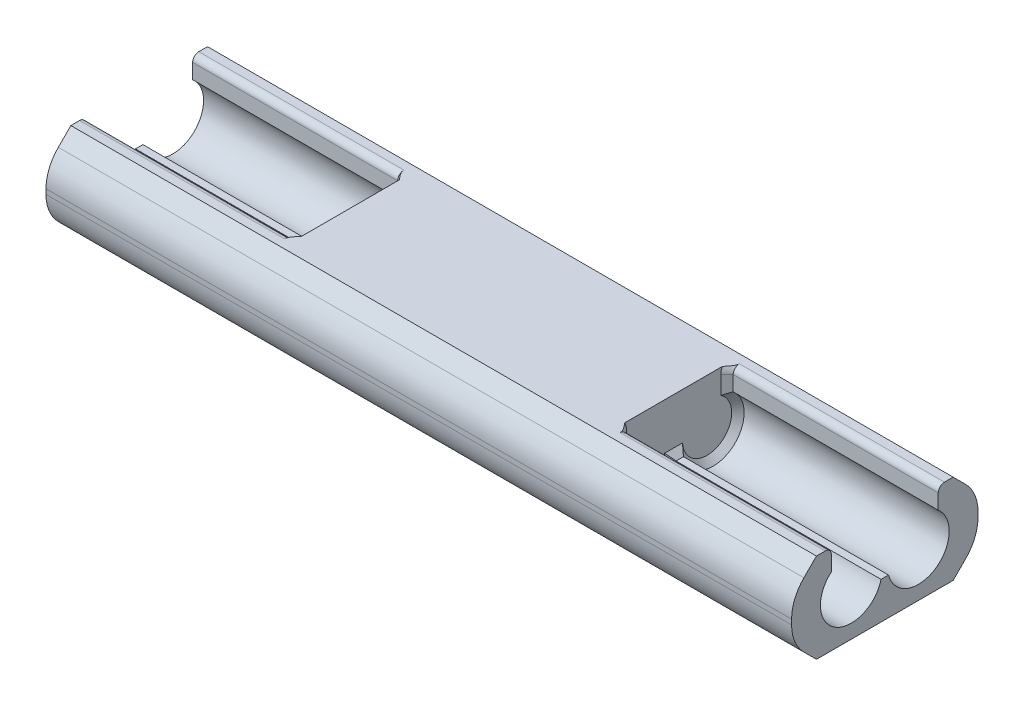
SolidWorks part; units mm, degrees
ref_plane "Front Plane" through (0, 0, 0) normal (0, 0, 1) x (1, 0, 0)
ref_plane "Top Plane" through (0, 0, 0) normal (0, 1, 0) x (1, 0, 0)
ref_plane "Right Plane" through (0, 0, 0) normal (1, 0, 0) x (0, 0, -1)
other "Configuration Table"
sketch "Sketch1" plane through (0, 0, 0) normal (1, 0, 0) x (0, 0, -1)
  line L0 (-1.7145, 0) -> (1.7145, 0) construction
  line L1 (-1.7145, 2.286) -> (-1.7145, 0) construction
  line L2 (3.4925, -2.286) -> (-3.4925, -2.286)
  line L3 (4.7625, -0.127) -> (4.7625, 0.127)
  line L4 (3.4925, 2.286) -> (-3.4925, 2.286)
  line L5 (-4.7625, -0.127) -> (-4.7625, 0.127)
  line L6 (4.7625, -2.286) -> (-4.7625, 2.286) construction
  line L7 (4.7625, 2.286) -> (-4.7625, -2.286) construction
  line L8 (-1.7145, 0) -> (-4.7625, 0) construction
  line L9 (3.4925, -2.286) -> (4.1339, -1.6446)
  line L10 (4.1339, 1.6446) -> (3.4925, 2.286)
  line L11 (-4.1339, 1.6446) -> (-3.4925, 2.286)
  line L12 (-4.1339, -1.6446) -> (-3.4925, -2.286)
  line L13 (0, -2.286) -> (0, 2.286) construction
  line L14 (-3.4925, 2.286) -> (-4.7625, 2.286) construction
  line L15 (-4.7625, 1.016) -> (-4.7625, 2.286) construction
  line L16 (-4.7625, -2.286) -> (-4.7625, -1.016) construction
  line L17 (-3.4925, -2.286) -> (-4.7625, -2.286) construction
  line L18 (4.7625, -2.286) -> (3.4925, -2.286) construction
  line L19 (4.7625, -2.286) -> (4.7625, -1.016) construction
  line L20 (4.7625, 1.016) -> (4.7625, 2.286) construction
  line L21 (4.7625, 2.286) -> (3.4925, 2.286) construction
  circle A0 centre (-1.7145, 0) radius 1.5
  circle A1 centre (1.7145, 0) radius 1.5
  arc A2 (-4.1339, 1.6446) -> (-4.7625, 0.127) centre (-2.6163, 0.127) ccw
  arc A3 (-4.1339, -1.6446) -> (-4.7625, -0.127) centre (-2.6163, -0.127) cw
  arc A4 (4.1339, -1.6446) -> (4.7625, -0.127) centre (2.6163, -0.127) ccw
  arc A5 (4.7625, 0.127) -> (4.1339, 1.6446) centre (2.6163, 0.127) ccw
  point P5 (0, 0)
extrude "Boss-Extrude1" add sketch "Sketch1" along normal blind 19.05 contours L2 L12 A3 L5 A2 L11 L4 L10 A5 L3 A4 L9
sketch "Sketch2" plane through (19.05, 0, 0) normal (1, 0, 0) x (0, 0, -1)
  line L0 (-2.7305, 1.2035) -> (-2.7305, 2.286)
  line L1 (3.4925, 2.286) -> (-3.4925, 2.286) construction
  line L2 (-2.7305, 2.286) -> (2.7305, 2.286)
  line L3 (2.7305, 2.286) -> (2.7305, 1.2035)
  line L4 (2.7305, 1.2035) -> (0.1905, -0.3976)
  line L5 (0.1905, -0.3976) -> (-0.1905, -0.3976)
  line L6 (-0.1905, -0.3976) -> (-2.7305, 1.2035)
  circle A0 centre (1.7145, 0) radius 1.5 construction
  circle A1 centre (-1.7145, 0) radius 1.5 construction
  circle A2 centre (1.7145, 0) radius 1.5 construction
  circle A3 centre (-1.7145, 0) radius 1.5 construction
  circle A4 centre (-1.7145, 0) radius 1.575
  circle A5 centre (1.7145, 0) radius 1.575
  line M16 (3.4925, 2.286) -> (-3.4925, 2.286)
extrude "Cut-Extrude1" cut sketch "Sketch2" against normal blind 10.795 contours L6 A4 | A5 L3 L0 A4 L5 M16 | L6 A4 | L4 A5 | L4 A5 region at (19.05, 0.7887, 1.2173) region at (19.05, 1.6466, 0) region at (19.05, -0.3551, 1.9383) region at (19.05, 0.7887, -1.2173) region at (19.05, -0.3551, -1.9383)
fillet "Fillet1" radius 0.3175 2 edges at (13.6525, 2.286, -2.7305) (13.6525, 2.286, 2.7305)
chamfer "Chamfer1" distance 0.3175 angle 45 7 edges at (8.255, 2.193, -2.8235) (8.255, 1.586, -2.7305) (8.255, -1.3324, -2.5543) (8.255, -0.3976, 0) (8.255, 2.193, 2.8235) (8.255, 1.586, 2.7305) (8.255, -1.3324, 2.5543)
mirror "Mirror1" about plane through (0, 0, 0) normal (1, 0, 0) of bodies 102
equation "\"Width\"= 1.5in"
equation "\"D4@Sketch1\"=\"ProfileWidth\""
equation "\"Height\"= 0.18in"
equation "\"D3@Sketch1\"=\"ProfileHeight\""
equation "\"DowelSpacing\"= 0.135in"
equation "\"D1@Sketch1\"=\"DowelSpacing\""
equation "\"D1@Boss-Extrude1\"=\"Width\"/2"
equation "\"ProfileWidth\"= .375in"
equation "\"ProfileHeight\"= .18in"
equation "\"DowelClearance\"= 3mm + .15mm"
equation "\"D1@Sketch2\"=\"DowelClearance\""
equation "\"D1@Cut-Extrude1\"=\"DowelDepth\""
equation "\"InnerWidth\"= .65in"
equation "\"DowelDepth\"= ( \"Width\" - \"InnerWidth\" ) / 2"
